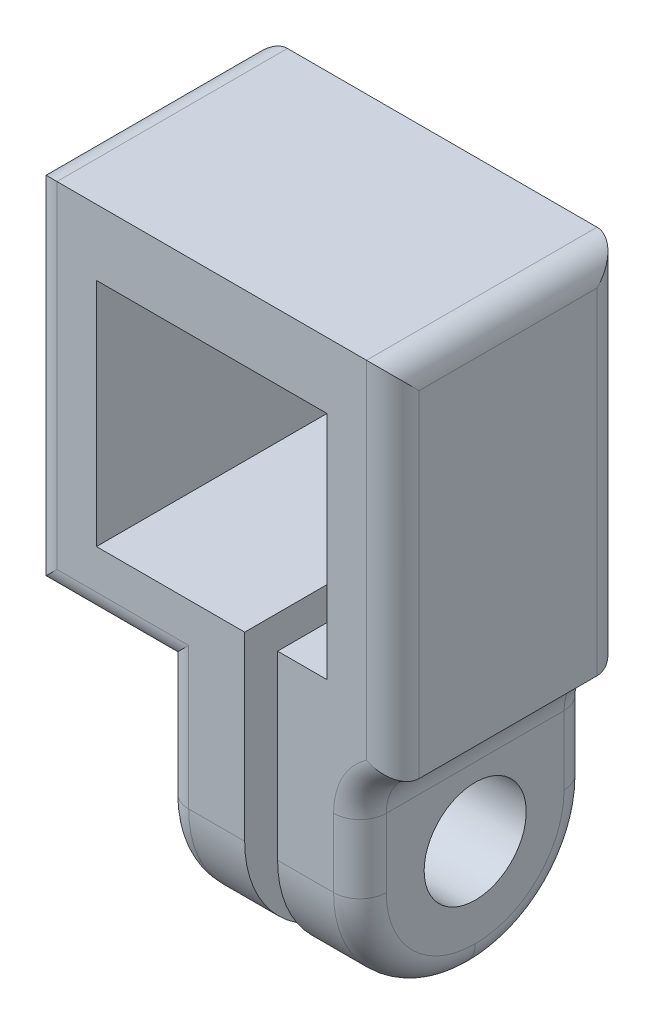
SolidWorks part; units mm, degrees
ref_plane "前视基准面" through (0, 0, 0) normal (0, 0, 1) x (1, 0, 0)
ref_plane "上视基准面" through (0, 0, 0) normal (0, 1, 0) x (1, 0, 0)
ref_plane "右视基准面" through (0, 0, 0) normal (1, 0, 0) x (0, 0, -1)
sketch "草图1" plane through (0, 0, 0) normal (0, 0, 1) x (1, 0, 0)
  line L0 (0, 6.4547) -> (0, -8.4381) construction
  line L1 (2, -2.5) -> (2.5, -2.5)
  line L2 (-3.5, -2.5) -> (-3.5, 4.5)
  line L3 (-2.5, -2.5) -> (1, -2.5)
  line L5 (-2.5, 2.5) -> (2.5, -2.5) construction
  line L6 (-2.5, -2.5) -> (2.5, 2.5) construction
  line L7 (-3.5, 4.5) -> (3.5, 4.5)
  line L9 (-4.5, -4.5) -> (-1.5, -4.5)
  line L11 (-4.5, 4.5) -> (4.5, -4.5) construction
  line L12 (-4.5, -4.5) -> (4.5, 4.5) construction
  line L13 (4.5, -4.5) -> (4.5, -11.5)
  line L14 (4.5, -11.5) -> (2.5, -11.5)
  line L17 (0.5, -11.5) -> (-1.5, -11.5)
  line L18 (-1.5, -11.5) -> (-1.5, -4.5)
  line L20 (0.5, -11.5) -> (1, -11.5)
  line L21 (1, -11.5) -> (1, -2.5)
  line L22 (2.5, -11.5) -> (2, -11.5)
  line L23 (2, -11.5) -> (2, -2.5)
  line L24 (-4.5, -4.5) -> (-5.5, -4.5)
  line L25 (4.5, -4.5) -> (5.5, -4.5)
  line L26 (5.5, -4.5) -> (5.5, 6.5)
  line L27 (-5.5, -4.5) -> (-5.5, 6.5)
  line L28 (-5.5, 6.5) -> (5.5, 6.5)
  line L29 (-2.5, -2.5) -> (-3.5, -2.5)
  line L30 (2.5, -2.5) -> (3.5, -2.5)
  line L32 (3.5, -2.5) -> (3.5, 4.5)
  point P0 (0, 0)
  point P5 (0, 0)
  dimension "D1" = 5
  dimension "D2" = 5
  dimension "D3" = 9
  dimension "D4" = 9
  dimension "D5" = 7
  dimension "D8" = 2
  dimension "D9" = 0.5
  dimension "D10" = 0.5
  dimension "D11" = 1
  dimension "D12" = 1
  dimension "D13" = 11
  dimension "D14" = 11
  dimension "D15" = 1
  dimension "D16" = 1
  dimension "D17" = 7
  dimension "D18" = 7
extrude "凸台-拉伸1" add sketch "草图1" against normal blind 7
fillet "圆角1" radius 3.5 4 edges at (3.25, -11.5, 0) (3.25, -11.5, -7) (-0.25, -11.5, -7) (-0.25, -11.5, 0)
sketch "草图2" plane through (-1.5, 0, 0) normal (-1, 0, 0) x (0, 0, 1)
  circle A0 centre (-3.5, -8) radius 1.55
  dimension "D1" = 3.1
extrude "切除-拉伸1" cut sketch "草图2" against normal through all
fillet "圆角2" radius 1.5 1 edges at (4.5, -4.5, -3.5)
fillet "圆角3" radius 0.8 18 edges at (4.7753, -5.0482, -7) (4.5, -6.9571, -7) (4.5, -10.4749, -5.9749) (4.5, -10.4749, -1.0251) (4.7753, -5.0482, 0) (-1.5, -6.25, -7) (-1.5, -10.4749, -5.9749) (-1.5, -10.4749, -1.0251) (5.5, 6.5, -3.5) (5.5, 1, -7) (5.5, 1, 0) (4.5, -6.9571, 0) (-5.5, 6.5, -3.5) (-5.5, 1, -7) (-3.5, -4.5, -7) (-1.5, -6.25, 0) (-3.5, -4.5, 0) (-5.5, 1, 0)
